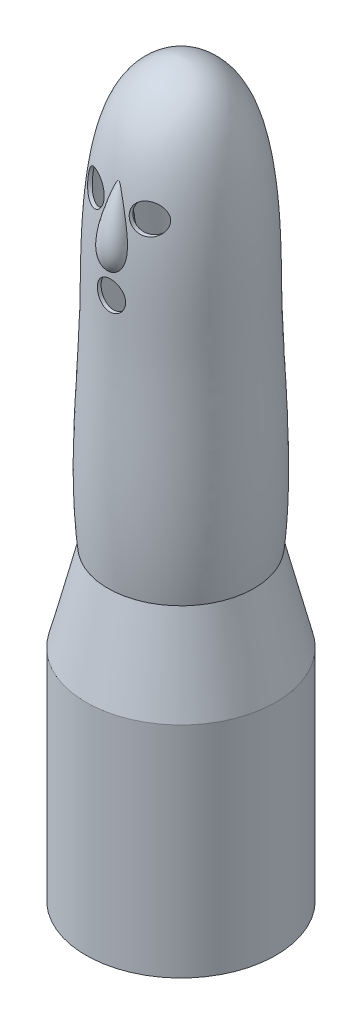
SolidWorks part; units mm, degrees
ref_plane "正面" through (0, 0, 0) normal (0, 0, 1) x (1, 0, 0)
ref_plane "平面" through (0, 0, 0) normal (0, 1, 0) x (1, 0, 0)
ref_plane "右側面" through (0, 0, 0) normal (1, 0, 0) x (0, 0, -1)
sketch "ｽｹｯﾁ3" plane through (0, 0, 0) normal (0, 0, 1) x (1, 0, 0)
  line L0 (0, 0) -> (0, 1000)
  line L1 (100, 420) -> (130, 300)
  line L2 (130, 300) -> (130, 0)
  line L3 (130, 0) -> (0, 0)
  spline S0 degree 3 poles (0, 1000) (63.349, 993.2668) (98.9639, 866.0662) (94.7686, 668.4306) (109.768, 515.2833) (100, 420) knots 0 0 0 0 0.273809 0.53402 1 1 1 1
  point P4 (0, 190.1576)
  point P9 (37.7117, 155.0366)
  point P10 (15.538, 188.6002)
  point P12 (32.8059, 151.9058)
  point P14 (41.2819, 90.4561)
  point P15 (36.3153, 115.864)
  point P16 (38.8232, 107.4724)
  point P17 (50, 64.1227)
  point P18 (0, 0)
  point P19 (0, 0)
  point P20 (0, 0)
  point P21 (40.8758, 103.9879)
  point P22 (0, 256.7367)
  point P23 (26.3384, 246.0107)
  point P24 (34.7148, 202.2326)
  point P25 (0, 282.5863)
  point P26 (25.0959, 269.957)
  point P27 (24.8612, 792.4759)
  point P28 (106.0301, 748.4826)
  point P29 (122.3485, 589.5722)
  point P30 (137.2939, 342.7567)
  point P31 (113.5698, 486.4336)
  point P32 (127.9748, 663.9099)
  point P33 (0, 800)
  point P34 (21.519, 797.0933)
  point P35 (115.7592, 462.4055)
  point P36 (125.7252, 328.0974)
  point P37 (107.5302, 734.2347)
  point P38 (93.0708, 563.8226)
  point P39 (76.7259, 724.4217)
  point P40 (123.0783, 308.185)
  point P41 (104.2315, 330.1962)
  point P42 (76.8316, 668.7667)
  point P43 (97.7479, 458.3049)
  point P44 (81.4984, 596.9584)
  point P45 (39.9575, 984.7244)
  point P46 (89.9189, 868.5212)
  point P47 (97.9489, 707.8618)
  point P48 (103.9837, 485.9254)
  dimension "D1" = 130
  dimension "D2" = 100
  dimension "D3" = 120
  dimension "D4" = 300
  dimension "D5" = 1000
revolve "回転1" add sketch "ｽｹｯﾁ3" angle 360 about L0
shell "ｼｪﾙ1" thickness 5 removed face at (0, 0, -130)
sketch "ｽｹｯﾁ5" plane through (0, 0, 0) normal (0, 0, 1) x (1, 0, 0)
  circle A0 centre (-36.7237, 867.2048) radius 19.942
  circle A1 centre (36.909, 867.2048) radius 19.2485
  circle A2 centre (0, 765.7035) radius 19.3745
  point P6 (-36.7237, 867.2048)
  point P7 (36.909, 867.2048)
  point P8 (0, 765.7035)
extrude "ｶｯﾄ - 押し出し1" cut sketch "ｽｹｯﾁ5" against normal blind 25 and the other way through all
sketch "ｽｹｯﾁ6" plane through (0, 0, 0) normal (1, 0, 0) x (0, 0, -1)
  line L0 (-93.332, 791.5693) -> (-78.7298, 912.3457)
  spline S0 degree 3 poles (-93.332, 791.5693) (-131.3732, 811.4247) (-88.7739, 882.9567) (-78.7298, 912.3457) knots 0 0 0 0 1 1 1 1
  spline S1 degree 3 poles (0, 1000) (-0.0832, 999.9911) (-0.2494, 999.9733) (-0.4984, 999.9458) (-0.9121, 999.8991) (-1.7064, 999.8053) (-3.4017, 999.5855) (-5.6624, 999.2381) (-8.3259, 998.7456) (-10.7941, 998.2134) (-13.2508, 997.6058) (-15.6573, 996.9341) (-18.047, 996.1856) (-20.3869, 995.3705) (-22.6672, 994.4956) (-24.9021, 993.5558) (-27.089, 992.5529) (-29.2011, 991.5026) (-31.2299, 990.4137) (-33.202, 989.2772) (-35.1674, 988.0647) (-37.1423, 986.7598) (-39.1142, 985.3654) (-41.0665, 983.8911) (-42.9951, 982.3364) (-44.8858, 980.7115) (-46.7637, 978.9949) (-48.6009, 977.2078) (-50.4352, 975.311) (-52.2265, 973.3443) (-54.0169, 971.2559) (-55.8059, 969.0398) (-57.5863, 966.6944) (-59.3166, 964.2694) (-60.9953, 961.7721) (-62.6274, 959.1963) (-64.2127, 956.54) (-65.7238, 953.8563) (-67.1876, 951.1062) (-68.6341, 948.2295) (-70.0464, 945.2505) (-71.3861, 942.2566) (-72.6493, 939.2722) (-73.8582, 936.2563) (-75.04, 933.1426) (-76.2249, 929.8427) (-77.3918, 926.3969) (-78.511, 922.8886) (-79.5911, 919.3026) (-80.643, 915.5979) (-81.6696, 911.753) (-82.6512, 907.8462) (-83.6114, 903.7849) (-84.5609, 899.5039) (-85.4775, 895.0876) (-86.3431, 890.6338) (-87.1787, 886.0497) (-87.9989, 881.2422) (-88.8265, 876.0464) (-89.4581, 871.7891) (-90.176, 866.7112) (-90.8951, 861.3094) (-91.7273, 854.4504) (-92.4536, 847.8981) (-93.1133, 841.3477) (-93.7202, 834.671) (-94.2786, 827.8108) (-94.7755, 820.9113) (-95.2076, 814.0874) (-95.5822, 807.3457) (-95.9205, 800.3376) (-96.191, 793.7685) (-96.3529, 789.2208) (-96.4303, 786.8878) (-96.4584, 786.022) (-96.4777, 785.4187) (-96.4876, 785.1041) (-96.4884, 785.078) knots 0 0 0 0 0.000977 0.001953 0.002928 0.005842 0.011299 0.022902 0.032565 0.042947 0.052402 0.062134 0.072137 0.08166 0.091083 0.100672 0.109987 0.119193 0.128232 0.136888 0.145787 0.155212 0.164545 0.174003 0.183796 0.193488 0.20313 0.213523 0.223433 0.233959 0.244604 0.255572 0.267236 0.279007 0.290378 0.302394 0.314635 0.326522 0.33838 0.351036 0.364143 0.376901 0.38936 0.40201 0.414865 0.428275 0.442977 0.457374 0.471303 0.486737 0.502374 0.517804 0.533805 0.551137 0.569042 0.586508 0.604152 0.62349 0.643494 0.66563 0.67378 0.703419 0.729305 0.754514 0.78045 0.806233 0.832852 0.860876 0.887062 0.912748 0.939773 0.969047 0.989572 0.992948 0.996322 0.999695 1 1 1 1 construction
  point P3 (-95.5135, 808.5285)
  point P7 (-91.7585, 881.1678)
  point P8 (-95.3939, 810.6995)
  point P9 (-78.7298, 912.3457)
  point P10 (-93.332, 791.5693)
  point P11 (-96.2041, 793.2655)
revolve "回転2" add sketch "ｽｹｯﾁ6" angle 360 about L0
